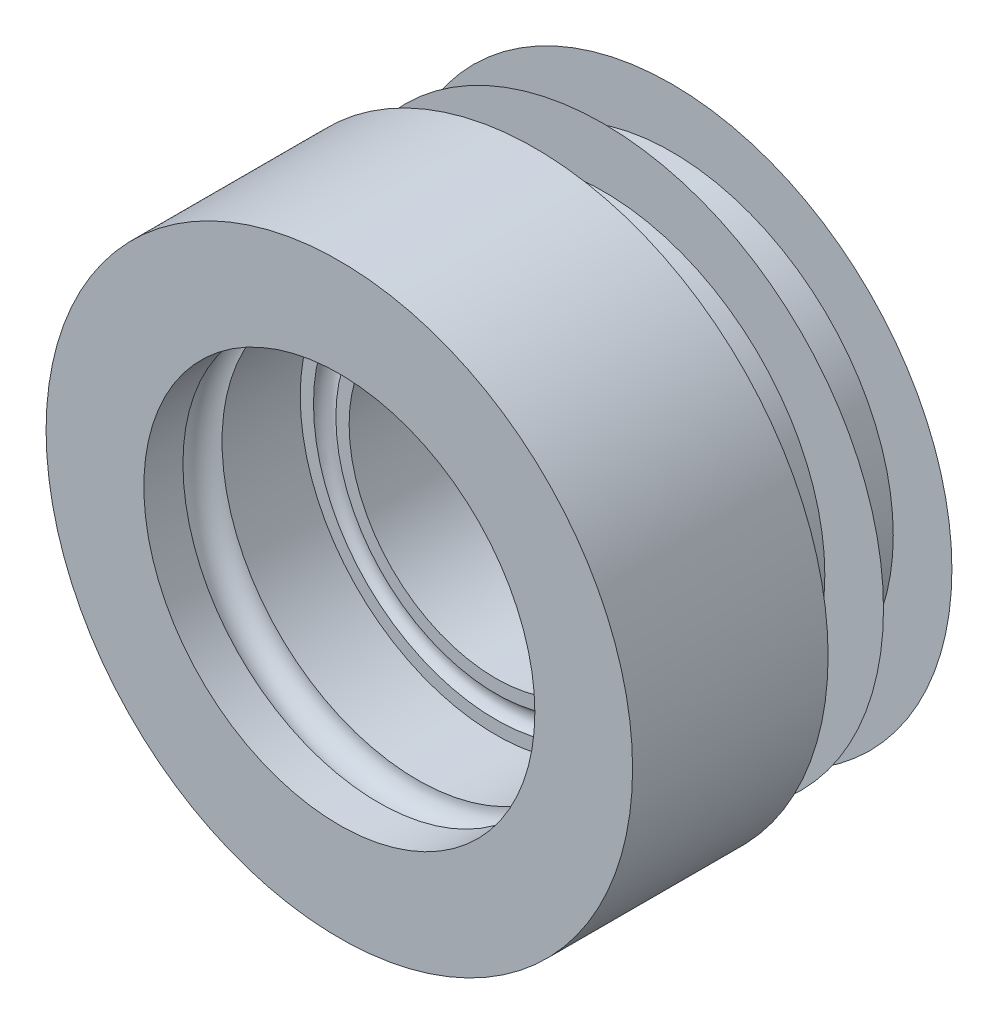
SolidWorks part; units mm, degrees
ref_plane "Front Plane" through (0, 0, 0) normal (0, 0, 1) x (1, 0, 0)
ref_plane "Top Plane" through (0, 0, 0) normal (0, 1, 0) x (1, 0, 0)
ref_plane "Right Plane" through (0, 0, 0) normal (1, 0, 0) x (0, 0, -1)
sketch "Sketch1" plane through (0, 0, 0) normal (0, 0, 1) x (1, 0, 0)
  circle A0 centre (0, 0) radius 15
  dimension "D1" = 30
extrude "Boss-Extrude1" add sketch "Sketch1" along normal blind 10
sketch "Sketch2" plane through (0, 0, 10) normal (0, 0, 1) x (1, 0, 0)
  circle A0 centre (0, 0) radius 10
  circle A1 centre (0, 0) radius 15 construction
  dimension "D1" = 5
extrude "Cut-Extrude1" cut sketch "Sketch2" against normal through all
sketch "Sketch4" plane through (0, 0, 0) normal (1, 0, 0) x (0, 0, -1)
  line L0 (0, 0) -> (-10, 0) construction
  line L1 (-10, 15) -> (-10, -15) construction
sketch "Sketch3" plane through (0, 0, 0) normal (1, 0, 0) x (0, 0, -1)
  line L0 (-10, 10) -> (-10, -10) construction
  circle A0 centre (-7, 10) radius 1
  dimension "D1" = 2
  dimension "D2" = 3
  dimension "D3" = 0
revolve "Cut-Revolve2" cut sketch "Sketch3" angle 360 about L0
sketch "Sketch5" plane through (0, 0, 0) normal (1, 0, 0) x (0, 0, -1)
  line L1 (-2, -7.5) -> (9, -7.5)
  line L2 (-2, -7.5) -> (-2, -11)
  line L3 (-2, -11) -> (9, -11)
  line L4 (9, -7.5) -> (9, -11)
  dimension "D1" = 1
  dimension "D2" = 3.5
  dimension "D3" = 11
  dimension "D4" = 4
revolve "Revolve1" add sketch "Sketch5" angle 360 about L0
sketch "Sketch7" plane through (0, 0, 0) normal (1, 0, 0) x (0, 0, -1)
  circle A0 centre (-2.25, 8.75) radius 0.625
  dimension "D1" = 1.25
  dimension "D2" = 1.25
  dimension "D3" = 0.25
revolve "Cut-Revolve3" cut sketch "Sketch7" angle 360 about L0
sketch "Sketch9" plane through (0, 0, 0) normal (0, 0, -1) x (-1, 0, 0)
  circle A0 centre (0, 0) radius 11.3327
extrude "Boss-Extrude2" add sketch "Sketch9" along normal blind 9
sketch "Sketch10" plane through (0, 0, -9) normal (0, 0, -1) x (-1, 0, 0)
  circle A0 centre (0, 0) radius 7.5
  dimension "D1" = 15
extrude "Cut-Extrude2" cut sketch "Sketch10" against normal through all
sketch "Sketch11" plane through (0, 0, 0) normal (1, 0, 0) x (0, 0, -1)
  line L0 (9, 11.3327) -> (7, 11.3327)
  line L1 (9, 11.3327) -> (0, 11.3327) construction
  line L2 (7, 11.3327) -> (7, 14.3327)
  line L3 (7, 14.3327) -> (9, 11.3327)
  dimension "D1" = 2
  dimension "D2" = 3
revolve "Revolve2" add sketch "Sketch11" angle 360 about L0
pattern_linear "LPattern1" count 3 spacing 3.5 along (0, 0, 1) of "Revolve2"
